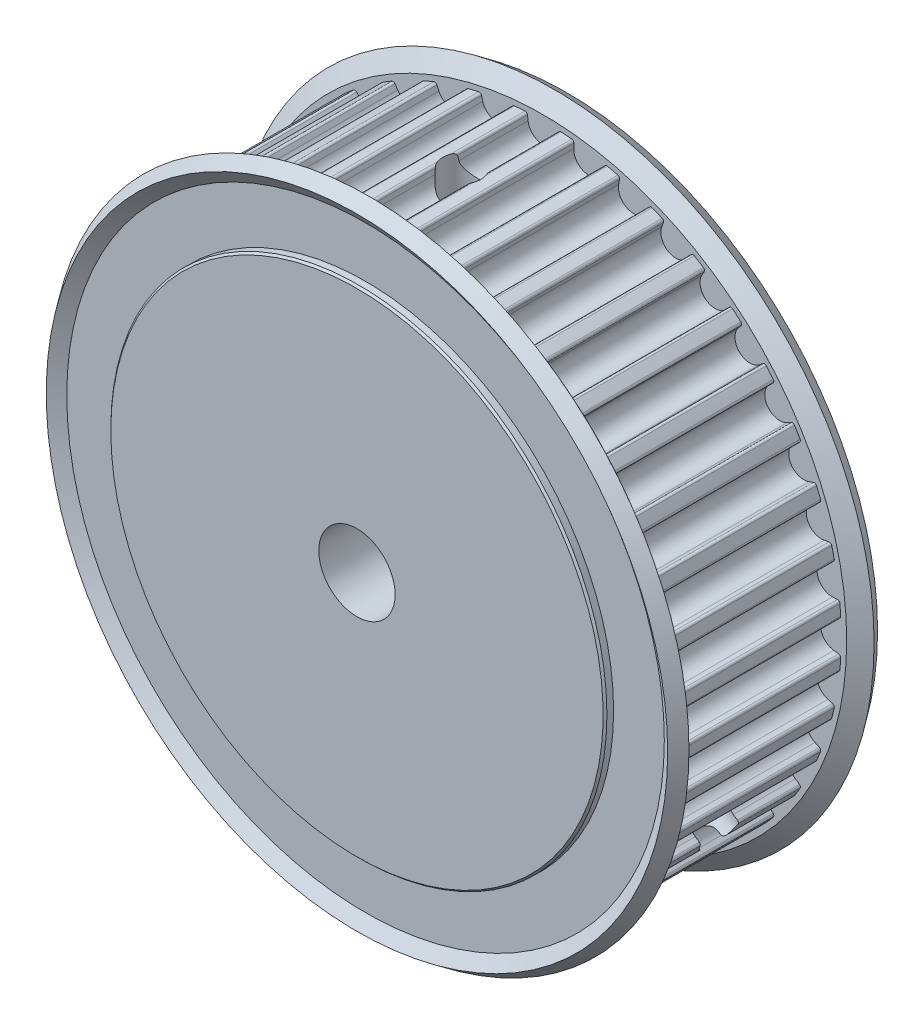
SolidWorks part; units mm, degrees
ref_plane "前视基准面" through (0, 0, 0) normal (0, 0, 1) x (1, 0, 0)
ref_plane "上视基准面" through (0, 0, 0) normal (0, 1, 0) x (1, 0, 0)
ref_plane "右视基准面" through (0, 0, 0) normal (1, 0, 0) x (0, 0, -1)
sketch "草图1" plane through (0, 0, 0) normal (1, 0, 0) x (0, 0, -1)
  line L0 (-34.7811, 0) -> (33.6192, 0) construction
  line L1 (0, 52.9736) -> (0, -62.0281) construction
  line L2 (-8.5, 31.26) -> (-8.5, 31.83)
  line L3 (-8.5, 31.83) -> (-9.701, 33.5)
  line L4 (-9.701, 33.5) -> (-11, 32.5658)
  line L5 (-11, 32.5658) -> (-10.1, 31.3144)
  line L6 (-10.1, 31.3144) -> (-10.1, 26)
  line L7 (-10.1, 26) -> (-11, 26)
  line L8 (10.1, 26) -> (11, 26)
  line L9 (10.1, 31.3144) -> (10.1, 26)
  line L10 (11, 32.5658) -> (10.1, 31.3144)
  line L11 (9.701, 33.5) -> (11, 32.5658)
  line L12 (8.5, 31.83) -> (9.701, 33.5)
  line L13 (8.5, 31.26) -> (8.5, 31.83)
  line L14 (8.5, -31.26) -> (8.5, -31.83)
  line L15 (8.5, -31.83) -> (9.701, -33.5)
  line L16 (9.701, -33.5) -> (11, -32.5658)
  line L17 (11, -32.5658) -> (10.1, -31.3144)
  line L18 (10.1, -31.3144) -> (10.1, -26)
  line L19 (10.1, -26) -> (11, -26)
  line L20 (-10.1, -26) -> (-11, -26)
  line L21 (-10.1, -31.3144) -> (-10.1, -26)
  line L22 (-11, -32.5658) -> (-10.1, -31.3144)
  line L23 (-9.701, -33.5) -> (-11, -32.5658)
  line L24 (-8.5, -31.83) -> (-9.701, -33.5)
  line L25 (-8.5, -31.26) -> (-8.5, -31.83)
  line L26 (-11, 26) -> (-11, -26)
  line L27 (11, 26) -> (11, -26)
  line L28 (-8.5, 31.26) -> (8.5, 31.26)
  line L29 (-8.5, -31.26) -> (8.5, -31.26)
  point P33 (0, 31.26)
  dimension "D1" = 2.5
  dimension "F" = 67
  dimension "D2" = 1.6
  dimension "E" = 52
  dimension "D3" = 1.6
  dimension "W" = 22
  dimension "D4" = 63.66
  dimension "A" = 17
  dimension "D5" = 62.52
sketch "草图2" plane through (0, 0, 0) normal (0, 0, 1) x (1, 0, 0)
  line L0 (-18.7064, 0) -> (19.5832, 0) construction
  line L1 (0, 30.5033) -> (0, -25.8377) construction
  line L2 (0, 0) -> (0, 31.26) construction
  line L3 (1.5635, 30.4833) -> (1.625, 30.9838)
  line L7 (0, 52.9736) -> (0, -62.0281) construction
  line L8 (-1.5, 3.7081) -> (-1.5, 5.4)
  line L9 (1.5, 3.7081) -> (1.5, 5.4)
  line L10 (-1.5, 5.4) -> (1.5, 5.4)
  line L11 (-1.5635, 30.4833) -> (-1.625, 30.9838)
  circle A0 centre (0, 0) radius 31.26
  circle A1 centre (0, 0) radius 31.83 construction
  circle A6 centre (0, 0) radius 2.5
  circle A7 centre (0, 0) radius 4
  arc A11 (-1.5635, 30.4833) -> (1.5635, 30.4833) centre (0, 30.6753) ccw
  arc A12 (-1.625, 30.9838) -> (-1.8882, 31.2029) centre (-1.8731, 30.9534) ccw
  arc A13 (1.625, 30.9838) -> (1.8882, 31.2029) centre (1.8731, 30.9534) cw
  point P7 (0, 31.83)
  point P8 (0, 31.26)
  point P13 (31.26, 0)
  dimension "PD" = 63.66
  dimension "OD" = 62.52
  dimension "H" = 5
  dimension "N" = 8
  dimension "D3" = 0.5
  dimension "D4" = 2.16
  dimension "D5" = 3.25
  dimension "D1" = 7
  dimension "b" = 3
  dimension "t" = 1.4
sketch "草图3" plane through (0, 0, 0) normal (1, 0, 0) x (0, 0, -1)
  line L0 (-11, 26) -> (-11, -26) construction
  line L1 (11, 26) -> (11, -26) construction
  line L2 (11, 32.5658) -> (10.1, 31.3144) construction
  line L3 (10.1, 26) -> (11, 26) construction
  line L4 (10.1, 31.3144) -> (10.1, 26) construction
  line L5 (-10.1, 31.3144) -> (-10.1, 26) construction
  line L6 (-11, 26) -> (-11, 0)
  line L7 (11, 26) -> (11, 0)
  line L8 (9.701, 33.5) -> (11, 32.5658) construction
  line L9 (10.1, 26) -> (11, 26)
  line L10 (10.1, 31.3144) -> (10.1, 26)
  line L11 (-10.1, 31.3144) -> (-10.1, 26)
  line L12 (8.5, 31.83) -> (9.701, 33.5) construction
  line L13 (8.5, 31.26) -> (8.5, 31.83) construction
  line L14 (-8.5, 31.26) -> (8.5, 31.26) construction
  line L15 (-8.5, 31.26) -> (-8.5, 31.83) construction
  line L16 (-8.5, 31.83) -> (-9.701, 33.5) construction
  line L17 (-9.701, 33.5) -> (-11, 32.5658) construction
  line L18 (-11, 32.5658) -> (-10.1, 31.3144) construction
  line L19 (11, 32.5658) -> (10.1, 31.3144)
  line L20 (9.701, 33.5) -> (11, 32.5658)
  line L21 (8.5, 31.83) -> (9.701, 33.5)
  line L22 (8.5, 31.26) -> (8.5, 31.83)
  line L23 (-8.5, 31.26) -> (8.5, 31.26)
  line L24 (-8.5, 31.26) -> (-8.5, 31.83)
  line L25 (-8.5, 31.83) -> (-9.701, 33.5)
  line L26 (-9.701, 33.5) -> (-11, 32.5658)
  line L27 (-11, 32.5658) -> (-10.1, 31.3144)
  line L28 (-34.7811, 0) -> (33.6192, 0) construction
  line L29 (-34.7811, 0) -> (33.6192, 0) construction
  line L30 (-11, 0) -> (11, 0)
  line L31 (-10.1, 26) -> (-11, 26) construction
  line L32 (-10.1, 26) -> (-11, 26)
revolve "旋转1" add sketch "草图3" angle 360 about L29
sketch "草图4" plane through (0, 0, 0) normal (0, 0, 1) x (1, 0, 0)
  line L3 (-1.5635, 30.4833) -> (-1.625, 30.9838) construction
  line L4 (1.5635, 30.4833) -> (1.625, 30.9838) construction
  line L5 (-1.5635, 30.4833) -> (-1.625, 30.9838)
  line L6 (1.5635, 30.4833) -> (1.625, 30.9838)
  arc A5 (-1.625, 30.9838) -> (-1.8882, 31.2029) centre (-1.8731, 30.9534) ccw construction
  arc A6 (-1.5635, 30.4833) -> (1.5635, 30.4833) centre (0, 30.6753) ccw construction
  arc A7 (1.8882, 31.2029) -> (1.625, 30.9838) centre (1.8731, 30.9534) ccw construction
  circle A8 centre (0, 0) radius 31.26 construction
  arc A9 (-1.625, 30.9838) -> (-1.8882, 31.2029) centre (-1.8731, 30.9534) ccw
  arc A10 (-1.5635, 30.4833) -> (1.5635, 30.4833) centre (0, 30.6753) ccw
  arc A11 (1.8882, 31.2029) -> (1.625, 30.9838) centre (1.8731, 30.9534) ccw
  arc A12 (1.8882, 31.2029) -> (-1.8882, 31.2029) centre (0, 0) ccw
extrude "切除-拉伸1" cut sketch "草图4" along normal up to vertex (8.5 mm away) from vertex up to point (0, 31.26, 8.5) starting at point (0, 31.26, -8.5)
pattern_circular "阵列(圆周)1" count 40 over 360 about axis through (0, 0, 34.7811) along (0, 0, 1) of "切除-拉伸1"
sketch "草图5" plane through (0, 0, 0) normal (0, 0, 1) x (1, 0, 0)
  circle A0 centre (0, 0) radius 2.5 construction
  circle A1 centre (0, 0) radius 2.5
extrude "H" [suppressed] cut sketch "草图5" along normal up to vertex from vertex up to point (0, 26, 11) starting at point (0, 26, -11)
sketch "草图6" plane through (0, 0, 0) normal (0, 0, 1) x (1, 0, 0)
  line L0 (-1.5, 5.4) -> (1.5, 5.4) construction
  line L1 (1.5, 3.7081) -> (1.5, 5.4) construction
  line L2 (-1.5, 3.7081) -> (-1.5, 5.4) construction
  line L3 (-1.5, 5.4) -> (1.5, 5.4)
  line L4 (1.5, 3.7081) -> (1.5, 5.4)
  line L5 (-1.5, 3.7081) -> (-1.5, 5.4)
  circle A0 centre (0, 0) radius 4 construction
  arc A1 (-1.5, 3.7081) -> (1.5, 3.7081) centre (0, 0) ccw
extrude "N" cut sketch "草图6" along normal up to vertex (11 mm away) from vertex up to point (0, 26, 11) starting at point (0, 26, -11)
sketch "草图8" plane through (0, 0, 0) normal (0, 0, 1) x (1, 0, 0)
  line L0 (-1.5, 3.7081) -> (-1.5, 5.4) construction
  line L1 (-1.5, 5.4) -> (1.5, 5.4) construction
  line L2 (1.5, 3.7081) -> (1.5, 5.4) construction
  line L3 (-1.5, 3.7081) -> (-1.5, 5.4)
  line L4 (-1.5, 5.4) -> (1.5, 5.4)
  line L5 (1.5, 3.7081) -> (1.5, 5.4)
  circle A0 centre (0, 0) radius 4 construction
  arc A1 (1.5, 3.7081) -> (-1.5, 3.7081) centre (0, 0) ccw
extrude "P" add sketch "草图8" against normal up to vertex from vertex up to point (0, 26, -11) starting at point (0, 26, 11)
sketch "草图7" plane through (0, 0, 0) normal (0, 1, 0) x (1, 0, 0)
  circle A0 centre (0, 0) radius 2
  dimension "M" = 4
extrude "螺纹孔1" cut sketch "草图7" along normal up to vertex up to point (0, 31.26, 0)
cosmetic thread "装饰螺纹线1" parameters "D2"=4.1
pattern_circular "螺纹孔2" count 2 every 120 about axis through (0, 0, 34.7811) along (0, 0, 1) of "螺纹孔1" reverse direction yes
chamfer "倒角1" distance 0.2 angle 45 2 edges at (26, 0, -11) (26, 0, 11)
